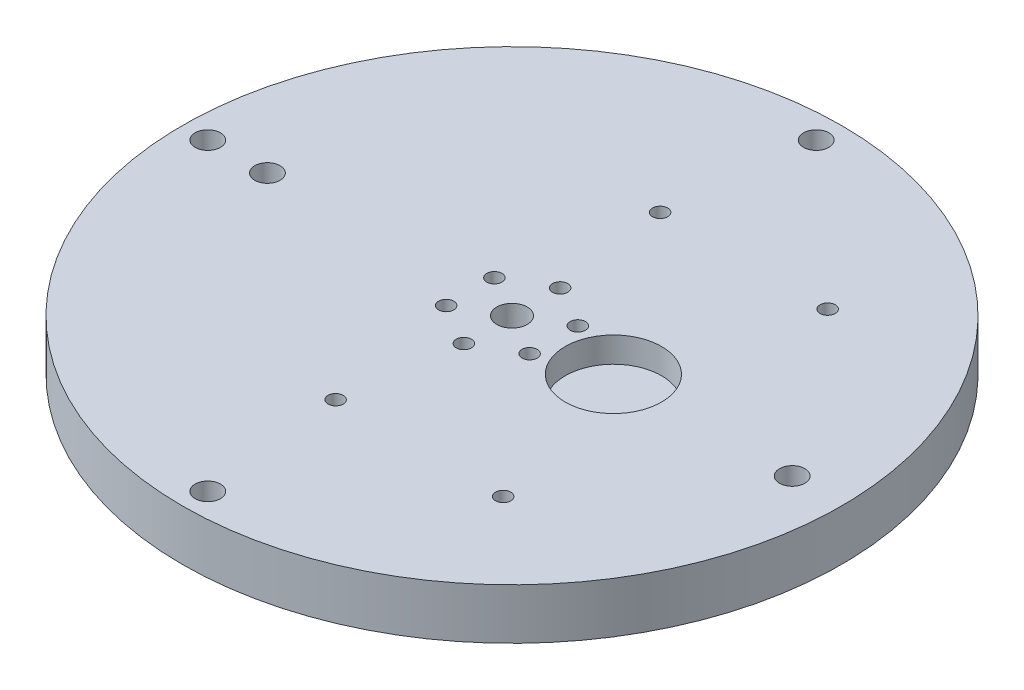
SolidWorks part; units mm, degrees
note: The reader was unsure of these and kept them because the rebuilt part matched: shared geometry of "Sketch1<3>".
ref_plane "Front Plane" through (0, 0, 0) normal (0, 0, 1) x (1, 0, 0)
ref_plane "Top Plane" through (0, 0, 0) normal (0, 1, 0) x (1, 0, 0)
ref_plane "Right Plane" through (0, 0, 0) normal (1, 0, 0) x (0, 0, -1)
sketch "Sketch1" plane through (0, 0, 0) normal (0, 1, 0) x (1, 0, 0)
  line L3 (0, 0) -> (0, 9.5) construction
  line L4 (0, -65) -> (0, 65) construction
  line L32 (-55, 0) -> (55, 0) construction
  circle A1 centre (0, 0) radius 3
  circle A2 centre (0, 9.5) radius 1.5
  circle A3 centre (8.2272, 4.75) radius 1.5
  circle A4 centre (8.2272, -4.75) radius 1.5
  circle A5 centre (0, -9.5) radius 1.5
  circle A6 centre (-8.2272, -4.75) radius 1.5
  circle A7 centre (-8.2272, 4.75) radius 1.5
  circle A19 centre (0, 0) radius 65
  circle A20 centre (0, 0) radius 55
  circle A21 centre (0, -60) radius 2.5
  circle A22 centre (-60, 0) radius 2.5
  circle A23 centre (0, 60) radius 2.5
  circle A25 centre (20, 0) radius 9.5
  circle A26 centre (-3.0487, 32.2608) radius 1.5 construction
  circle A27 centre (30.0013, 32.2608) radius 1.5 construction
  circle A28 centre (55.0013, 0.2608) radius 2.5 construction
  circle A29 centre (30.0013, -31.7392) radius 1.5 construction
  circle A30 centre (-3.0487, -31.7392) radius 1.5 construction
  circle A31 centre (-3.0487, 32.2608) radius 1.5
  circle A32 centre (30.0013, 32.2608) radius 1.5
  circle A33 centre (55.0013, 0.2608) radius 2.5
  circle A34 centre (30.0013, -31.7392) radius 1.5
  circle A35 centre (-3.0487, -31.7392) radius 1.5
  circle A36 centre (60, 0) radius 2.5 [skipped]
  point P21 (0, 0)
  point P22 (0, 30)
  point P31 (0, 0)
  point P34 (0, -30)
  dimension "D1" = 130
  dimension "D3" = 6
  dimension "D4" = 3
  dimension "D11" = 30
  dimension "D12" = 19
  dimension "D7" = 5
  dimension "D6" = 110
  dimension "D8" = 60
  dimension "D2" = 9.5
  dimension "D9" = 4
  dimension "D10" = 30
  dimension "D13" = 20
  dimension "D5" = 6
extrude "Boss-Extrude1" add sketch "Sketch1" along normal blind 10
extrude "Boss-Extrude2" add sketch "Sketch1<3>" along normal blind 5 contours A25
sketch "Sketch1<3>" plane through (0, 0, 0) normal (0, 1, 0) x (1, 0, 0) same geometry as "Sketch1"
sketch "Sketch2" plane through (0, 0, 0) normal (0, -1, 0) x (1, 0, 0)
  circle A0 centre (30.0013, 31.7392) radius 5
  circle A1 centre (-3.0487, 31.7392) radius 5
  circle A2 centre (55.0013, -0.2608) radius 5
  circle A3 centre (30.0013, -32.2608) radius 5
  circle A4 centre (-3.0487, -32.2608) radius 5
  dimension "D1" = 10
  dimension "D2" = 10
  dimension "D3" = 10
  dimension "D4" = 10
  dimension "D5" = 10
extrude "Cut-Extrude1" cut sketch "Sketch2" against normal blind 5
sketch "Sketch3" plane through (0, 10, 0) normal (0, 1, 0) x (1, 0, 0)
  circle A0 centre (-48.4987, 0.2608) radius 2.5 construction
  circle A1 centre (-48.4987, 0.2608) radius 2.5
extrude "Cut-Extrude2" cut sketch "Sketch3" against normal blind 10
sketch "Sketch4" plane through (0, 0, 0) normal (0, -1, 0) x (1, 0, 0)
  circle A0 centre (-48.4987, -0.2608) radius 5
  dimension "D1" = 10
extrude "Cut-Extrude3" cut sketch "Sketch4" against normal blind 5
